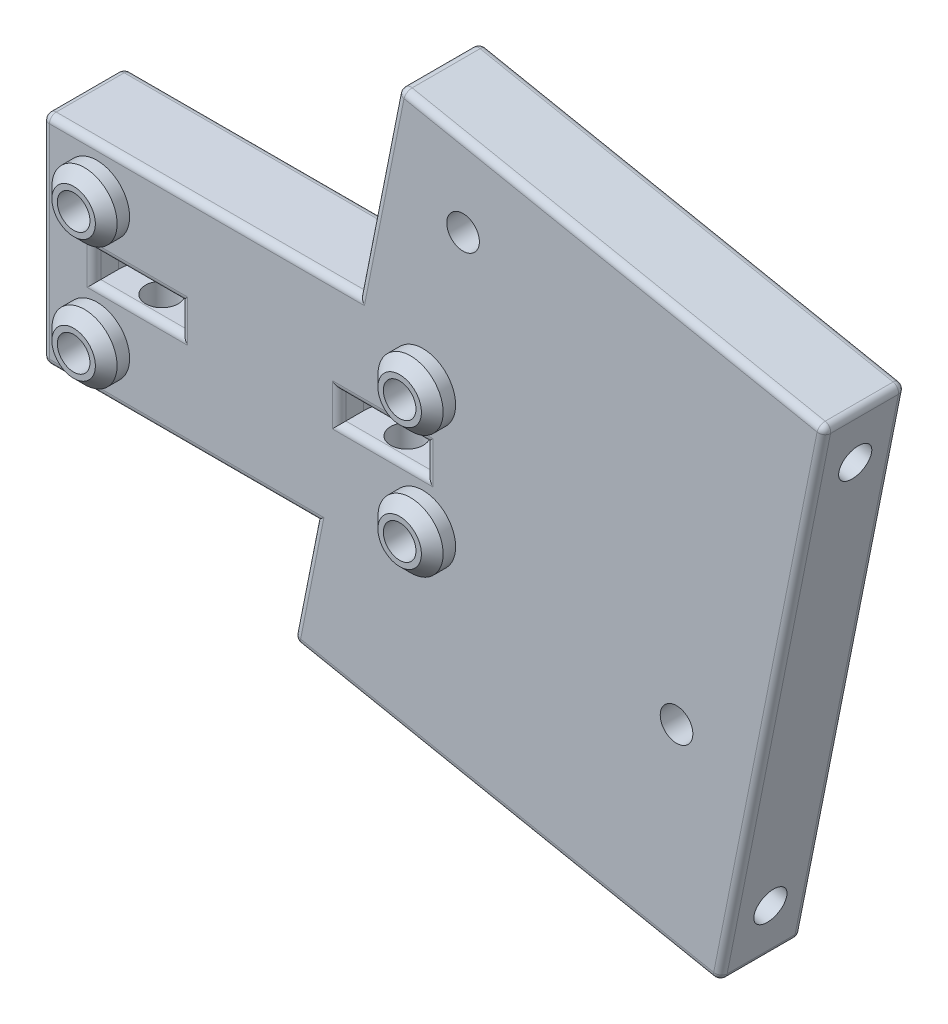
SolidWorks part; units mm, degrees
ref_plane "Front Plane" through (0, 0, 0) normal (0, 0, 1) x (1, 0, 0)
ref_plane "Top Plane" through (0, 0, 0) normal (0, 1, 0) x (1, 0, 0)
ref_plane "Right Plane" through (0, 0, 0) normal (1, 0, 0) x (0, 0, -1)
sketch "Sketch1" plane through (0, 0, 0) normal (0, 0, 1) x (1, 0, 0)
  line L2 (-38.1, -12.7) -> (-38.1, 12.7)
  line L3 (-38.1, 12.7) -> (38.1, 12.7)
  line L10 (38.1, -12.7) -> (38.1, 12.7)
  line L11 (-38.1, -12.7) -> (38.1, -12.7)
  line L14 (-38.1, 12.7) -> (38.1, -12.7) construction
  point P2 (0, 0)
  dimension "D1" = 76.2
  dimension "D2" = 25.4
extrude "Boss-Extrude1" add sketch "Sketch1" along normal blind 9.525
sketch "Sketch6" plane through (0, 0, 9.525) normal (0, 0, -1) x (-1, 0, 0)
  line L4 (8.8811, -26.1846) -> (-40.9428, -36.0952)
  line L6 (8.8811, -26.1846) -> (-3.5072, 36.0952)
  line L23 (-40.9428, -36.0952) -> (-53.3311, 26.1846)
  line L24 (-3.5072, 36.0952) -> (-53.3311, 26.1846)
  line L25 (8.8811, -26.1846) -> (-53.3311, 26.1846) construction
  line L26 (-40.9428, -36.0952) -> (-3.5072, 36.0952) construction
  line L27 (-38.1, 12.7) -> (38.1, 12.7) construction
  point P1 (-22.225, 0)
  dimension "D1" = 50.8
  dimension "D2" = 63.5
  dimension "D3" = 11.25
  dimension "D4" = 0
  dimension "D5" = 22.225
extrude "Boss-Extrude2" add sketch "Sketch6" along normal up to surface (9.525 mm away) up to face at (0, 0, 0)
sketch "Sketch4" plane through (0, 0, 0) normal (0, 1, 0) x (1, 0, 0)
  line L7 (-1.1464, -9.525) -> (-38.1, -9.525) construction
  line L8 (-32.0992, -6.6675) -> (-32.0992, -9.525)
  line L9 (-21.9392, -6.6675) -> (-21.9392, -9.525)
  line L10 (-21.9392, -9.525) -> (-32.0992, -9.525)
  line L11 (-38.1, -9.525) -> (-38.1, 0) construction
  arc A2 (-21.9392, -6.6675) -> (-32.0992, -6.6675) centre (-27.0192, -6.6675) ccw
  dimension "D1" = 10.16
  dimension "D2" = 2.8575
  dimension "D3" = 11.0808
extrude "Cut-Extrude2" cut sketch "Sketch4" against normal mid plane 3.302
ref_plane "Plane3" through (-12.7, 0, 0) normal (-1, 0, 0) x (0, 0, 1)
sketch "Sketch2" plane through (0, 0, 9.525) normal (0, 0, 1) x (1, 0, 0)
  line L1 (-38.1, 12.7) -> (-38.1, -12.7) construction
  line L2 (0, 0) -> (-38.1, 0) construction
  line L3 (-38.1, 12.7) -> (-38.1, -12.7) construction
  circle A0 centre (-31.75, 7.1755) radius 1.905
  circle A1 centre (-31.75, -7.1755) radius 1.905
  dimension "D1" = 3.81
  dimension "D2" = 14.351
  dimension "D3" = 6.35
extrude "Cut-Extrude1" cut sketch "Sketch2" against normal through all both and the other way through all
sketch "Sketch11" plane through (0, 0, 9.525) normal (0, 0, 1) x (1, 0, 0)
  circle A0 centre (-31.75, 7.1755) radius 3.81
  circle A1 centre (-31.75, 7.1755) radius 1.905
  circle A2 centre (-31.75, 7.1755) radius 1.905 construction
  circle A3 centre (-31.75, -7.1755) radius 3.81
  circle A4 centre (-31.75, -7.1755) radius 1.905
  dimension "D1" = 7.62
extrude "Boss-Extrude5" add sketch "Sketch11" along normal blind 2.7305
sketch "Sketch5" plane through (0, 12.7, 0) normal (0, 1, 0) x (1, 0, 0)
  line L0 (-1.1464, -9.525) -> (-38.1, -9.525) construction
  line L1 (-38.1, -9.525) -> (-38.1, 0) construction
  circle A0 centre (-27.0192, -6.6675) radius 1.905
  dimension "D3" = 3.81
  dimension "D1" = 2.8575
  dimension "D2" = 11.0808
extrude "Cut-Extrude3" cut sketch "Sketch5" against normal through all from offset 6.35 offset against normal yes
mirror "Mirror1" about plane through (-12.7, 0, 0) normal (-1, 0, 0) of "Cut-Extrude1", "Cut-Extrude3", "Cut-Extrude2", "Boss-Extrude5"
chamfer "Chamfer4" distance 1.27 angle 45 4 edges at (-27.94, -7.1755, 12.2555) (2.54, -7.1755, 12.2555) (2.54, 7.1755, 12.2555) (-27.94, 7.1755, 12.2555)
fillet "Fillet3" radius 0.7937 30 edges at (-38.1, 0, 9.525) (-38.1, -12.7, 4.7625) (-38.1, 0, 0) (-38.1, 12.7, 4.7625) (-19.6232, 12.7, 0) (-19.6232, 12.7, 9.525) (1.1804, 24.3976, 9.525) (1.1804, 24.3976, 0) (3.5072, 36.0952, 4.7625) (28.4191, 31.1399, 0) (28.4191, 31.1399, 9.525) (53.3311, 26.1846, 4.7625) (47.1369, -4.9553, 0) (47.1369, -4.9553, 9.525) (40.9428, -36.0952, 4.7625) (16.0309, -31.1399, 0) (16.0309, -31.1399, 9.525) (-8.8811, -26.1846, 4.7625) (-7.5399, -19.4423, 9.525) (-7.5399, -19.4423, 0) (-22.1494, -12.7, 0) (-22.1494, -12.7, 9.525) (1.6193, -1.651, 9.525) (6.6993, 0, 9.525) (1.6193, 1.651, 9.525) (-3.4607, 0, 9.525) (-21.9392, 0, 9.525) (-32.0992, 0, 9.525) (-27.0192, 1.651, 9.525) (-27.0192, -1.651, 9.525)
sketch "Sketch12" plane through (46.2911, -9.2079, 0) normal (0.9808, -0.1951, 0) x (0, 0, -1)
  circle A6 centre (-4.7625, -21.0641) radius 1.905
  circle A7 centre (-4.7625, 29.7359) radius 1.905
  dimension "D1" = 3.81
extrude "Cut-Extrude4" cut sketch "Sketch12" against normal blind 9.525
sketch "Sketch13" plane through (-3.5328, 0.7027, 0) normal (-0.9808, 0.1951, 0) x (0, 0, 1)
  circle A0 centre (4.7625, 29.7359) radius 1.905
  circle A1 centre (4.7625, -21.0641) radius 1.905
  dimension "D1" = 3.81
extrude "Cut-Extrude5" cut sketch "Sketch13" against normal blind 9.525
sketch "Sketch14" plane through (0, 0, 0) normal (0, 0, -1) x (-1, 0, 0)
  circle A8 centre (-11.0294, 25.0886) radius 1.905
  circle A9 centre (-35.9752, -12.2455) radius 1.905
  dimension "D1" = 3.81
  dimension "D2" = 3.81
extrude "Cut-Extrude6" cut sketch "Sketch14" against normal through all
